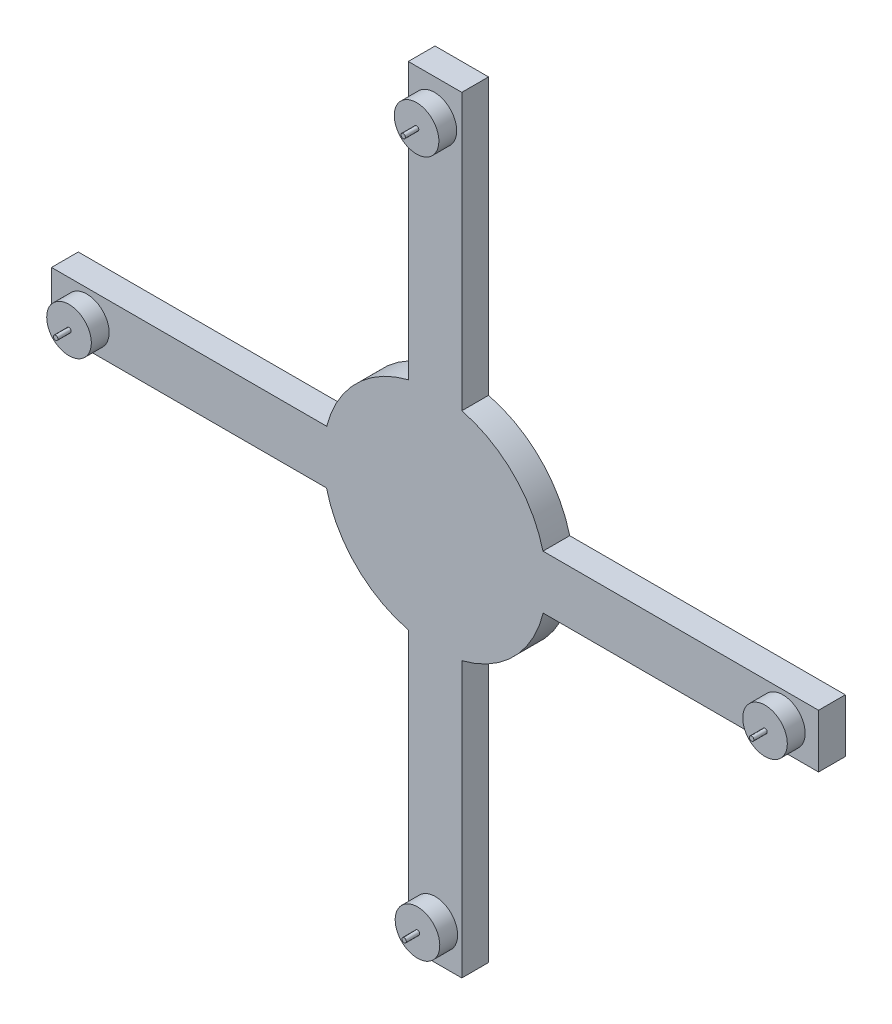
SolidWorks part; units mm, degrees
material "Nylon 101"
ref_plane "Front Plane" through (0, 0, 0) normal (0, 0, 1) x (1, 0, 0)
ref_plane "Top Plane" through (0, 0, 0) normal (0, 1, 0) x (1, 0, 0)
ref_plane "Right Plane" through (0, 0, 0) normal (1, 0, 0) x (0, 0, -1)
sketch "Sketch1" plane through (0, 0, 0) normal (0, 0, 1) x (1, 0, 0)
  line L0 (-30, 430) -> (30, 430)
  line L1 (30, 430) -> (30, 30)
  line L2 (30, 30) -> (430, 30)
  line L3 (430, 30) -> (430, -30)
  line L4 (430, -30) -> (30, -30)
  line L5 (30, -30) -> (30, -430)
  line L6 (30, -430) -> (-30, -430)
  line L7 (-30, -430) -> (-30, -30)
  line L8 (-30, -30) -> (-430, -30)
  line L9 (-430, -30) -> (-430, 30)
  line L10 (-430, 30) -> (-30, 30)
  line L11 (-30, 30) -> (-30, 430)
  circle A0 centre (-0.208, -0.5161) radius 125
  circle A1 centre (0, 0) radius 42.4264
  dimension "D3" = 250
  dimension "D1" = 400
  dimension "D2" = 60
extrude "Boss-Extrude1" add sketch "Sketch1" along normal blind 15 and the other way blind 15 contours L1 L0 L11 | A1 L1 L11 | A1 L4 L2 | L4 L3 L2 | L7 L6 L5 | A1 L10 L8 | A1 L7 L5 | L8 L7 | L5 L4 | L2 L1 | L11 L10 | L10 L9 L8 | A1 region at (0.0017, 276.6346, 0) region at (-0.006, 80.8479, 0) region at (-66.0265, 65.8286, 0) region at (65.8488, 65.7648, 0) region at (-81.2101, -0.0148, 0) region at (0, 0, 0) region at (-276.9962, 0.0041, 0) region at (81.0018, -0.0148, 0) region at (276.7882, 0.0041, 0) region at (-0.0059, -81.3649, 0) region at (-66.185, -66.2697, 0) region at (0.0017, -277.1507, 0) region at (66.0072, -66.2058, 0)
sketch "Sketch2" plane through (0, 0, 15) normal (0, 0, 1) x (1, 0, 0)
  line L0 (430, 30) -> (430, -30) construction
  circle A0 centre (390, 0) radius 25
  dimension "D1" = 50
  dimension "D2" = 40
extrude "Boss-Extrude2" add sketch "Sketch2" along normal blind 20
sketch "Sketch3" plane through (0, 0, 35) normal (0, 0, 1) x (1, 0, 0)
  circle A0 centre (390, 0) radius 2.5
  circle A1 centre (390, 0) radius 25 construction
  dimension "D1" = 5
extrude "Boss-Extrude3" add sketch "Sketch3" along normal blind 15
pattern_circular "CirPattern1" count 4 over 360 about axis through (-0.208, -0.5161, -15) along (0, 0, 1) of "Boss-Extrude2", "Boss-Extrude3"
